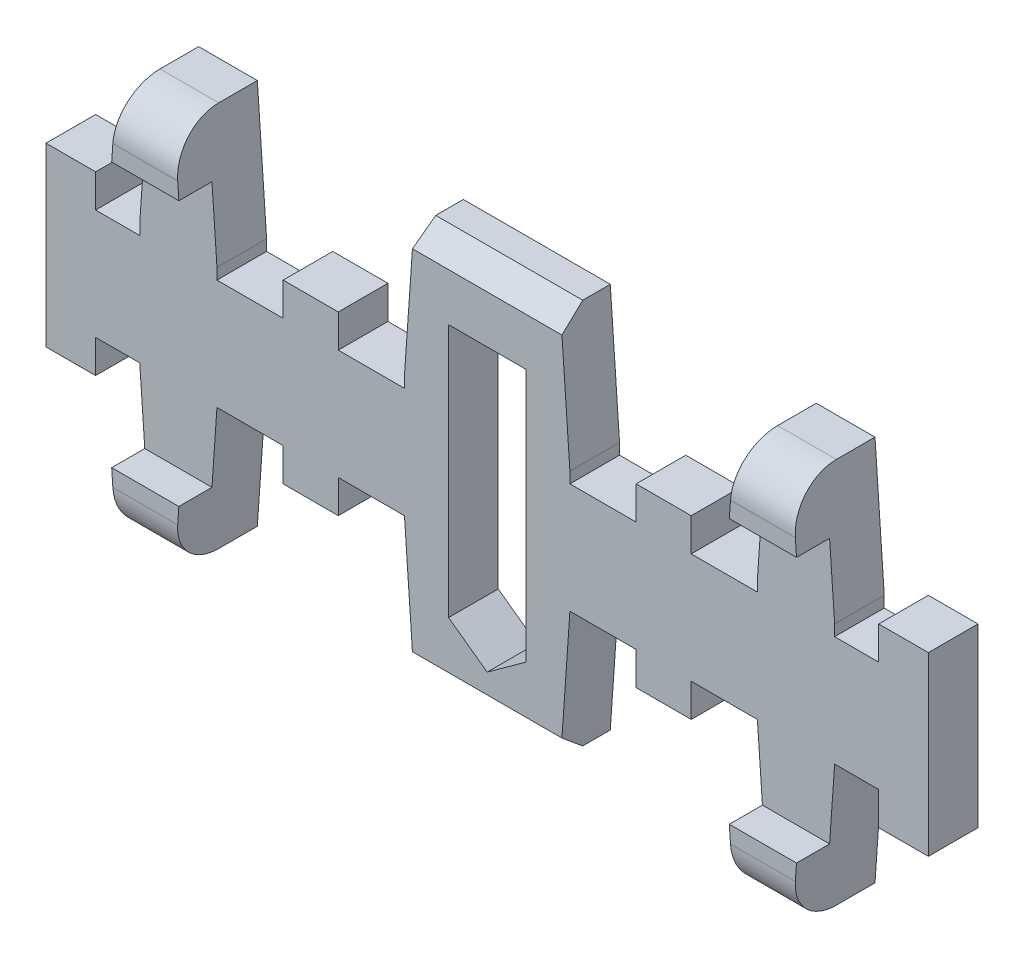
SolidWorks part; units mm, degrees
ref_plane "Plano frontal" through (0, 0, 0) normal (0, 0, 1) x (1, 0, 0)
ref_plane "Plano superior" through (0, 0, 0) normal (0, 1, 0) x (1, 0, 0)
ref_plane "Plano direito" through (0, 0, 0) normal (1, 0, 0) x (0, 0, -1)
sketch "Esboço10" plane through (0, 0, 0) normal (0, 0, 1) x (1, 0, 0)
  line L1 (-20, 8.75) -> (20, 8.75)
  line L2 (-20, 8.75) -> (-20, -8.75)
  line L3 (-20, -8.75) -> (20, -8.75)
  line L4 (20, 8.75) -> (20, -8.75)
  line L5 (-20, 8.75) -> (20, -8.75) construction
  line L6 (-20, -8.75) -> (20, 8.75) construction
  point P0 (0, 0)
  dimension "D1" = 40
  dimension "D2" = 17.5
extrude "Ressalto-extrusão6" add sketch "Esboço10" along normal blind 2.25
sketch "Esboço11" plane through (0, 0, 2.25) normal (0, 0, 1) x (1, 0, 0)
  line L0 (-20, 3.75) -> (-15.75, 3.75)
  line L1 (-20, 8.75) -> (-20, -8.75) construction
  line L2 (-15.75, 3.75) -> (-15.75, 8.75)
  line L3 (20, 8.75) -> (-20, 8.75) construction
  line L4 (-15.75, 8.75) -> (-12.25, 8.75)
  line L5 (-12.25, 8.75) -> (-12.25, 3.75)
  line L6 (-12.25, 3.75) -> (-3.75, 3.75)
  line L7 (-3.75, 3.75) -> (-3.75, 9.75)
  line L8 (-3.75, 9.75) -> (3.75, 9.75)
  line L9 (3.75, 9.75) -> (3.75, 3.75)
  line L10 (3.75, 3.75) -> (12.25, 3.75)
  line L11 (12.25, 3.75) -> (12.25, 8.75)
  line L12 (12.25, 8.75) -> (15.75, 8.75)
  line L13 (15.75, 8.75) -> (15.75, 3.75)
  line L14 (15.75, 3.75) -> (20, 3.75)
  line L15 (20, -8.75) -> (20, 8.75) construction
  line L16 (20, 3.75) -> (20, 11.9024)
  line L17 (20, 11.9024) -> (-20, 11.9024)
  line L18 (-20, 11.9024) -> (-20, 3.75)
  line L20 (-20, -4.25) -> (-15.75, -4.25)
  line L21 (-15.75, -4.25) -> (-15.75, -8.75)
  line L22 (-20, -8.75) -> (20, -8.75) construction
  line L23 (-15.75, -8.75) -> (-12.25, -8.75)
  line L24 (-12.25, -8.75) -> (-12.25, -4.25)
  line L25 (-12.25, -4.25) -> (-3.75, -4.25)
  line L26 (-3.75, -4.25) -> (-3.75, -10.25)
  line L27 (-3.75, -10.25) -> (3.75, -9.7467)
  line L28 (3.75, -9.7467) -> (3.75, -4.25)
  line L29 (3.75, -4.25) -> (12.25, -4.25)
  line L30 (12.25, -4.25) -> (12.25, -8.75)
  line L31 (12.25, -8.75) -> (15.75, -8.75)
  line L32 (15.75, -8.75) -> (15.75, -4.25)
  line L33 (15.75, -4.25) -> (20, -4.25)
  line L34 (20, -4.25) -> (20, -11.3192)
  line L35 (20, -11.3192) -> (-20, -11.3192)
  line L36 (-20, -11.3192) -> (-20, -4.25)
  point P4 (2, 4)
  dimension "D1" = 4.25
  dimension "D2" = 3.5
  dimension "D3" = 8.5
  dimension "D4" = 7.5
  dimension "D5" = 8.5
  dimension "D6" = 3.5
  dimension "D7" = 8
  dimension "D8" = 5
  dimension "D9" = 6
  dimension "D10" = 6
extrude "Corte-extrusão2" cut sketch "Esboço11" against normal blind 2.5
sketch "Esboço12" plane through (0, 0, 2.25) normal (0, 0, 1) x (1, 0, 0)
  line L0 (-12.25, 8.75) -> (-12.25, 3.75) construction
  line L1 (-15.75, 8.75) -> (-12.25, 8.75)
  line L2 (-15.75, 8.75) -> (-15.75, 6)
  line L3 (-15.75, 6) -> (-12.25, 6)
  line L4 (-12.25, 8.75) -> (-12.25, 6)
  line L6 (-15.75, -8.75) -> (-12.25, -8.75)
  line L7 (-15.75, -8.75) -> (-15.75, -6)
  line L8 (-15.75, -6) -> (-12.25, -6)
  line L9 (-12.25, -8.75) -> (-12.25, -6)
  line L11 (12.25, -8.75) -> (15.75, -8.75)
  line L12 (12.25, -8.75) -> (12.25, -6)
  line L13 (12.25, -6) -> (15.75, -6)
  line L14 (15.75, -8.75) -> (15.75, -6)
  line L16 (12.25, 8.75) -> (15.75, 8.75)
  line L17 (12.25, 8.75) -> (12.25, 6)
  line L18 (12.25, 6) -> (15.75, 6)
  line L19 (15.75, 8.75) -> (15.75, 6)
  point P28 (-12, 7)
  dimension "D1" = 2.75
  dimension "D2" = 2.75
  dimension "D3" = 2.75
  dimension "D4" = 2.75
extrude "Ressalto-extrusão7" add sketch "Esboço12" along normal blind 1.5
sketch "Esboço13" plane through (0, 0, 2.25) normal (0, 0, 1) x (1, 0, 0)
  line L1 (-12.25, 3.75) -> (-9.25, 3.75)
  line L2 (-12.25, 3.75) -> (-12.25, 2.25)
  line L3 (-12.25, 2.25) -> (-9.25, 2.25)
  line L4 (-9.25, 3.75) -> (-9.25, 2.25)
  line L5 (-3.75, 3.75) -> (-6.75, 3.75)
  line L6 (-3.75, 3.75) -> (-3.75, 2.25)
  line L7 (-3.75, 2.25) -> (-6.75, 2.25)
  line L8 (-6.75, 3.75) -> (-6.75, 2.25)
  line L9 (3.75, 3.75) -> (6.75, 3.75)
  line L10 (3.75, 3.75) -> (3.75, 2.25)
  line L11 (3.75, 2.25) -> (6.75, 2.25)
  line L12 (6.75, 3.75) -> (6.75, 2.25)
  line L13 (12.25, 3.75) -> (9.25, 3.75)
  line L14 (12.25, 3.75) -> (12.25, 2.25)
  line L15 (12.25, 2.25) -> (9.25, 2.25)
  line L16 (9.25, 3.75) -> (9.25, 2.25)
  line L17 (12.25, -4.25) -> (9.25, -4.25)
  line L18 (12.25, -4.25) -> (12.25, -2.75)
  line L19 (12.25, -2.75) -> (9.25, -2.75)
  line L20 (9.25, -4.25) -> (9.25, -2.75)
  line L21 (3.75, -4.25) -> (6.75, -4.25)
  line L22 (3.75, -4.25) -> (3.75, -2.75)
  line L23 (3.75, -2.75) -> (6.75, -2.75)
  line L24 (6.75, -4.25) -> (6.75, -2.75)
  line L25 (-3.75, -4.25) -> (-6.75, -4.25)
  line L26 (-3.75, -4.25) -> (-3.75, -2.75)
  line L27 (-3.75, -2.75) -> (-6.75, -2.75)
  line L28 (-6.75, -4.25) -> (-6.75, -2.75)
  line L29 (-12.25, -4.25) -> (-9.25, -4.25)
  line L30 (-12.25, -4.25) -> (-12.25, -2.75)
  line L31 (-12.25, -2.75) -> (-9.25, -2.75)
  line L32 (-9.25, -4.25) -> (-9.25, -2.75)
  line L33 (-15.75, -4.25) -> (-17.75, -4.25)
  line L34 (-15.75, -4.25) -> (-15.75, -2.75)
  line L35 (-15.75, -2.75) -> (-17.75, -2.75)
  line L36 (-17.75, -4.25) -> (-17.75, -2.75)
  line L37 (-15.75, 3.75) -> (-17.75, 3.75)
  line L38 (-15.75, 3.75) -> (-15.75, 2.25)
  line L39 (-15.75, 2.25) -> (-17.75, 2.25)
  line L40 (-17.75, 3.75) -> (-17.75, 2.25)
  line L41 (15.75, 3.75) -> (17.75, 3.75)
  line L42 (15.75, 3.75) -> (15.75, 2.25)
  line L43 (15.75, 2.25) -> (17.75, 2.25)
  line L44 (17.75, 3.75) -> (17.75, 2.25)
  line L45 (15.75, -4.25) -> (17.75, -4.25)
  line L46 (15.75, -4.25) -> (15.75, -2.75)
  line L47 (15.75, -2.75) -> (17.75, -2.75)
  line L48 (17.75, -4.25) -> (17.75, -2.75)
  dimension "D1" = 2
  dimension "D2" = 3
  dimension "D3" = 3
  dimension "D4" = 3
  dimension "D5" = 3
  dimension "D6" = 2
  dimension "D7" = 1.5
  dimension "D8" = 1.5
extrude "Corte-extrusão3" cut sketch "Esboço13" against normal blind 8
sketch "Esboço15" plane through (0, 0, 2.25) normal (0, 0, 1) x (1, 0, 0)
  line L0 (3.75, 8.75) -> (-3.75, 8.75) construction
  line L1 (-1.75, 5.75) -> (1.75, 5.75)
  line L2 (-1.75, 5.75) -> (-1.75, -5.75)
  line L3 (-1.75, -5.75) -> (0, -7.015)
  line L4 (1.75, 5.75) -> (1.75, -5.75)
  line L6 (-3.75, -8.75) -> (-3.75, -2.75) construction
  line L7 (3.75, -2.75) -> (3.75, -8.75) construction
  line L8 (0, -7.015) -> (1.75, -5.75)
  dimension "D1" = 3
  dimension "D3" = 2
  dimension "D4" = 2
extrude "Corte-extrusão4" cut sketch "Esboço15" against normal blind 20
chamfer "Chanfro5" distance 6 angle 4 12 edges at (-15.75, -8.75, 1.875) (-3.75, -8.75, 1.125) (12.25, -8.75, 1.875) (15.75, 8.75, 1.875) (3.75, 8.75, 1.125) (-12.25, 8.75, 1.875) (-12.25, -8.75, 1.875) (3.75, -8.75, 1.125) (15.75, -8.75, 1.875) (12.25, 8.75, 1.875) (-3.75, 8.75, 1.125) (-15.75, 8.75, 1.875)
chamfer "Chanfro6" distance 1 angle 40 2 edges at (0, -8.75, 2.25) (0, 8.75, 2.25)
fillet "Filete1" radius 2 4 edges at (-14, -8.75, 3.75) (-14, 8.75, 3.75) (14, 8.75, 3.75) (14, -8.75, 3.75)
